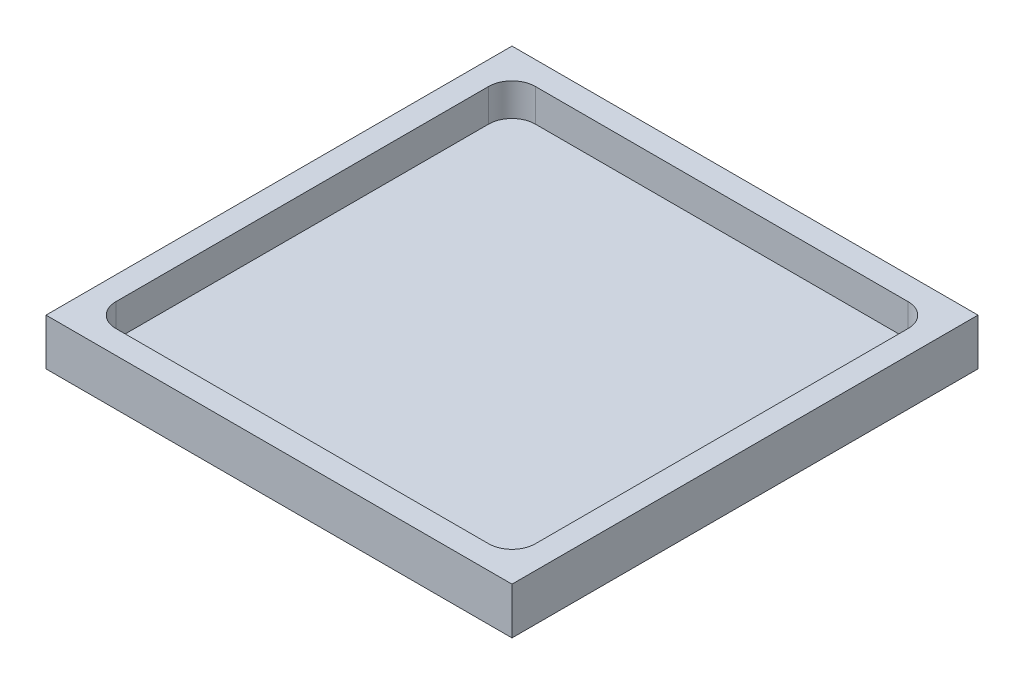
SolidWorks part; units mm, degrees
ref_plane "Front Plane" through (0, 0, 0) normal (0, 0, 1) x (1, 0, 0)
ref_plane "Top Plane" through (0, 0, 0) normal (0, 1, 0) x (1, 0, 0)
ref_plane "Right Plane" through (0, 0, 0) normal (1, 0, 0) x (0, 0, -1)
sketch "Sketch2" plane through (0, 0, 0) normal (0, 1, 0) x (1, 0, 0)
  line L1 (0, 0) -> (100, 0)
  line L2 (0, 0) -> (0, 100)
  line L3 (0, 100) -> (100, 100)
  line L4 (100, 0) -> (100, 100)
  dimension "D1" = 100
  dimension "D2" = 100
extrude "Boss-Extrude1" add sketch "Sketch2" along normal blind 10
sketch "Sketch3" plane through (0, 10, 0) normal (0, 1, 0) x (1, 0, 0)
  line L0 (100, 100) -> (0, 100) construction
  line L1 (5, 95) -> (95, 95)
  line L2 (5, 95) -> (5, 5)
  line L3 (5, 5) -> (95, 5)
  line L4 (95, 95) -> (95, 5)
  line L5 (0, 100) -> (0, 0) construction
  line L6 (50, 100) -> (50, 0) construction
  line L7 (0, 0) -> (100, 0) construction
  line L8 (0, 50) -> (100, 50) construction
  line L9 (100, 0) -> (100, 100) construction
  point P12 (50, 95)
  point P13 (50, 95)
  point P14 (50, 95)
  point P15 (5, 50)
  dimension "D1" = 5
  dimension "D2" = 5
extrude "Cut-Extrude1" cut sketch "Sketch3" against normal blind 7
fillet "Fillet1" [suppressed] radius 5
fillet "Fillet2" radius 5 4 edges at (95, 6.5, -95) (95, 6.5, -5) (5, 6.5, -5) (5, 6.5, -95)
